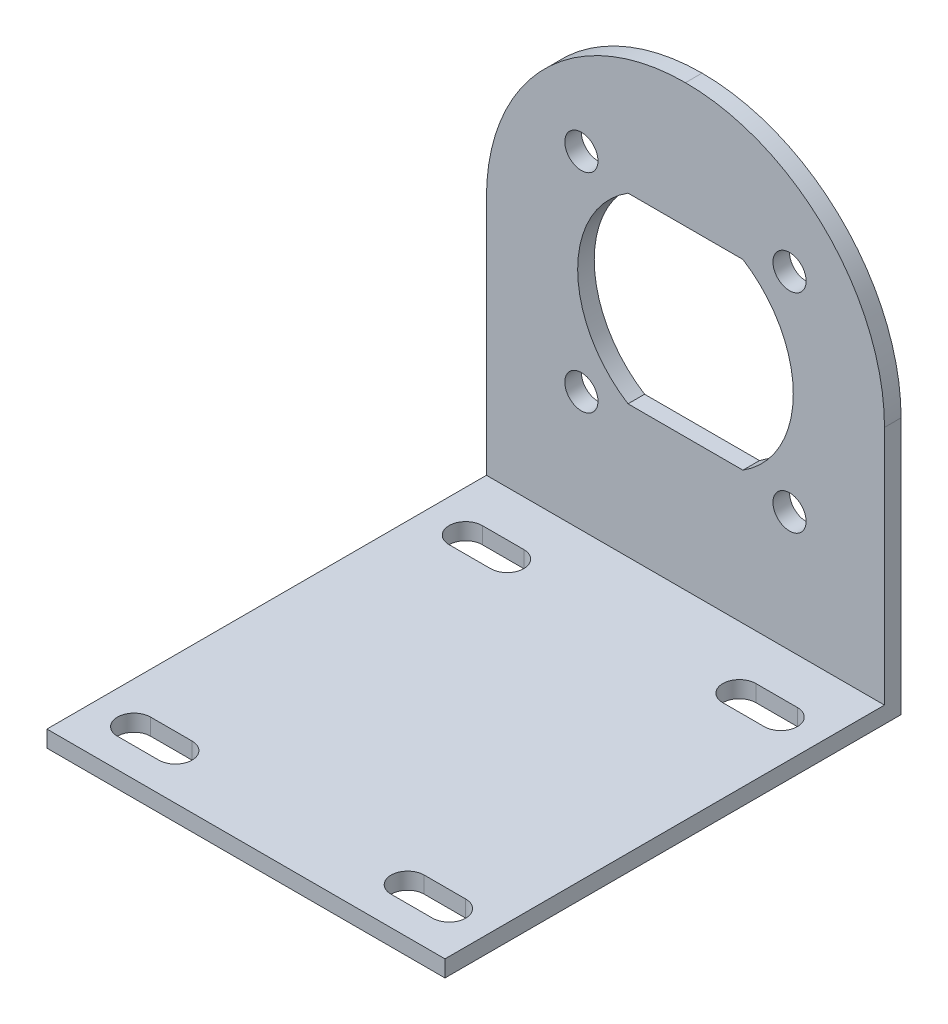
SolidWorks part; units mm, degrees
ref_plane "Front Plane" through (0, 0, 0) normal (0, 0, 1) x (1, 0, 0)
ref_plane "Top Plane" through (0, 0, 0) normal (0, 1, 0) x (1, 0, 0)
ref_plane "Right Plane" through (0, 0, 0) normal (1, 0, 0) x (0, 0, -1)
sketch "Sketch2" plane through (0, 0, 0) normal (0, 1, 0) x (1, 0, 0)
  line L1 (25, -26) -> (-25, -26)
  line L2 (25, -26) -> (25, 26)
  line L3 (25, 26) -> (-25, 26)
  line L4 (-25, -26) -> (-25, 26)
  line L5 (25, -26) -> (-25, 26) construction
  line L6 (25, 26) -> (-25, -26) construction
  point P0 (0, 0)
  dimension "D1" = 50
  dimension "D2" = 52
extrude "Boss-Extrude1" add sketch "Sketch2" along normal blind 52
sketch "Sketch3" plane through (0, 52, 0) normal (0, 1, 0) x (1, 0, 0)
  line L0 (-25, 26) -> (-25, -26)
  line L2 (-25, -26) -> (25, -26)
  line L7 (25, -26) -> (25, 24)
  line L8 (25, 24) -> (-25, 24)
  line M2 (-25, -26) -> (25, -26)
  line M3 (25, -26) -> (25, 26)
extrude "Cut-Extrude1" cut sketch "Sketch3" against normal blind 50 contours L8 L0 M3 M2 region at (0, 52, 1)
sketch "Sketch4" plane through (0, 0, -24) normal (0, 0, 1) x (1, 0, 0)
  line L0 (0, 18) -> (0, 40)
  line L9 (6.9282, 40) -> (-6.9282, 40)
  line L10 (-6.9282, 18) -> (6.9282, 18)
  circle A0 centre (0, 29) radius 5
  arc A5 (-6.9282, 40) -> (-6.9282, 18) centre (0, 29) ccw
  arc A6 (6.9282, 18) -> (6.9282, 40) centre (0, 29) ccw
  point P11 (0, 29)
  point P15 (0, 16)
  point P20 (0, 29)
  point P24 (0, 40)
  point P27 (0, 18)
  dimension "D1" = 10
  dimension "D2" = 22
  dimension "D3" = 13.8564
  dimension "D5" = 13
  dimension "D4" = 13.8564
extrude "Cut-Extrude3" cut sketch "Sketch4" against normal blind 50 contours L9 A5 L10 L0 A0 | L10 A6 L9 L0 A0 region at (-6.4219, 29, -24) region at (6.4219, 29, -24)
sketch "Sketch5" plane through (0, 0, -24) normal (0, 0, 1) x (1, 0, 0)
  line L5 (12.55, 16.45) -> (-12.55, 41.55) construction
  line L6 (12.55, 41.55) -> (-12.55, 16.45) construction
  circle A0 centre (12.55, 41.55) radius 2
  circle A1 centre (-12.55, 41.55) radius 2
  circle A2 centre (12.55, 16.45) radius 2
  circle A3 centre (-12.55, 16.45) radius 2
  point P0 (0, 29)
extrude "Cut-Extrude4" cut sketch "Sketch5" against normal blind 50
sketch "Sketch7" plane through (25, 0, 0) normal (1, 0, 0) x (0, 0, -1)
  line L1 (-26, 2) -> (26, 2)
  line L2 (-26, 2) -> (-26, 0)
  line L3 (-26, 0) -> (26, 0)
  line L4 (26, 2) -> (26, 0)
extrude "Boss-Extrude2" add sketch "Sketch7" along normal blind 5
mirror "Mirror1" about plane through (0, 0, 0) normal (1, 0, 0) of "Boss-Extrude2"
sketch "Sketch8" plane through (0, 2, 0) normal (0, 1, 0) x (1, 0, 0)
  line L0 (-30, -1) -> (30, -1) construction
  line L1 (-30, 24) -> (30, 24)
  line L2 (-30, 24) -> (-30, -26)
  line L3 (-30, -26) -> (30, -26)
  line L4 (30, 24) -> (30, -26)
  line L5 (-30, -1) -> (-29, -1)
  line L6 (0, -1) -> (0, 19.0878) construction
  circle A1 centre (-26.5, 14) radius 2.5
  circle A2 centre (26.5, 14) radius 2.5
  circle A3 centre (26.5, -16) radius 2.5
  circle A4 centre (-26.5, -16) radius 2.5
extrude "Cut-Extrude6" cut sketch "Sketch8" against normal blind 5 contours A1 | A4 | A2 | A3 region at (-26.5, 2, -14) region at (26.5, 2, -14) region at (26.5, 2, 16) region at (-26.5, 2, 16)
sketch "Sketch9" plane through (0, 0, 0) normal (0, -1, 0) x (1, 0, 0)
  line L0 (30, -26) -> (-30, -26) construction
  line L1 (-26.5, 16) -> (26.5, 16)
  line L2 (-26.5, 16) -> (-26.5, -14)
  line L3 (-26.5, -14) -> (26.5, -14)
  line L4 (26.5, 16) -> (26.5, -14)
  dimension "D1" = 53
  dimension "D2" = 30
  dimension "D3" = 12
sketch "Sketch10" plane through (0, 52, 0) normal (0, 1, 0) x (1, 0, 0)
  line L0 (24, 26) -> (-24, 26)
  line L1 (25, 26) -> (-25, 26) construction
  line L2 (-24, 26) -> (-24, 24)
  line L3 (25, 24) -> (-25, 24) construction
  line L4 (-24, 24) -> (24, 24)
  line L5 (24, 24) -> (24, 26)
  line L7 (-30, 26) -> (30, 26)
  line L8 (-30, 26) -> (-30, -26)
  line L9 (-30, -26) -> (30, -26)
  line L10 (30, 26) -> (30, -26)
  point P5 (0, 26)
  line M1 (-25, 24) -> (25, 24)
  line M2 (25, 24) -> (25, 26)
  line M3 (25, 26) -> (-25, 26)
  line M4 (-25, 26) -> (-25, 24)
extrude "Cut-Extrude7" cut sketch "Sketch10" against normal blind 160 contours L10 L7 L8 L9 M2 M1 M4 | L2 M3 M4 M1 | L5 M1 M2 M3 region at (24.5, 52, -25) region at (-24.5, 52, -25) region at (0, 52, 0.8278)
sketch "Sketch11" plane through (0, 52, 0) normal (0, 1, 0) x (1, 0, 0)
  line L1 (-24, 26) -> (24, 26)
  line L2 (-24, 26) -> (-24, 24)
  line L3 (-24, 24) -> (24, 24)
  line L4 (24, 26) -> (24, 24)
extrude "Boss-Extrude3" add sketch "Sketch11" along normal blind 3
sketch "Sketch12" plane through (0, 0, -24) normal (0, 0, 1) x (1, 0, 0)
  line L1 (-24, 0) -> (24, 0)
  line L2 (-24, 0) -> (-24, 2)
  line L3 (-24, 2) -> (24, 2)
  line L4 (24, 0) -> (24, 2)
  line L5 (24, 0) -> (24, 55) construction
  dimension "D1" = 2
  dimension "D2" = 48
extrude "Boss-Extrude4" add sketch "Sketch12" along normal blind 53
sketch "Sketch13" plane through (0, 2, 0) normal (0, 1, 0) x (1, 0, 0)
  line L1 (19, -3.5) -> (-19, -3.5) construction
  line L2 (0, -23.5) -> (0, 16.5) construction
  line L3 (19, 16.5) -> (14, 16.5) construction
  line L4 (-19, 16.5) -> (-14, 16.5) construction
  line L5 (19, 14.5) -> (14, 14.5)
  line L6 (19, 18.5) -> (14, 18.5)
  line L7 (-19, 14.5) -> (-14, 14.5)
  line L8 (-19, 18.5) -> (-14, 18.5)
  line L9 (-19, -23.5) -> (-14, -23.5) construction
  line L10 (-19, -21.5) -> (-14, -21.5)
  line L11 (-19, -25.5) -> (-14, -25.5)
  line L12 (19, -23.5) -> (14, -23.5) construction
  line L13 (19, -21.5) -> (14, -21.5)
  line L14 (19, -25.5) -> (14, -25.5)
  arc A0 (19, 14.5) -> (19, 18.5) centre (19, 16.5) ccw
  arc A1 (14, 18.5) -> (14, 14.5) centre (14, 16.5) ccw
  arc A2 (-19, 14.5) -> (-19, 18.5) centre (-19, 16.5) cw
  arc A3 (-14, 18.5) -> (-14, 14.5) centre (-14, 16.5) cw
  arc A4 (-19, -21.5) -> (-19, -25.5) centre (-19, -23.5) ccw
  arc A5 (-14, -25.5) -> (-14, -21.5) centre (-14, -23.5) ccw
  arc A6 (19, -21.5) -> (19, -25.5) centre (19, -23.5) cw
  arc A7 (14, -25.5) -> (14, -21.5) centre (14, -23.5) cw
  point P0 (0, -3.5)
  point P9 (0, -3.5)
  point P13 (16.5, 16.5)
  point P18 (-16.5, 16.5)
  point P25 (-16.5, -23.5)
  point P32 (16.5, -23.5)
  dimension "D1" = 2
extrude "Cut-Extrude9" cut sketch "Sketch13" against normal blind 53
fillet "Fillet1" radius 24 1 edges at (-24, 55, -25)
fillet "Fillet2" radius 24 1 edges at (24, 55, -25)
